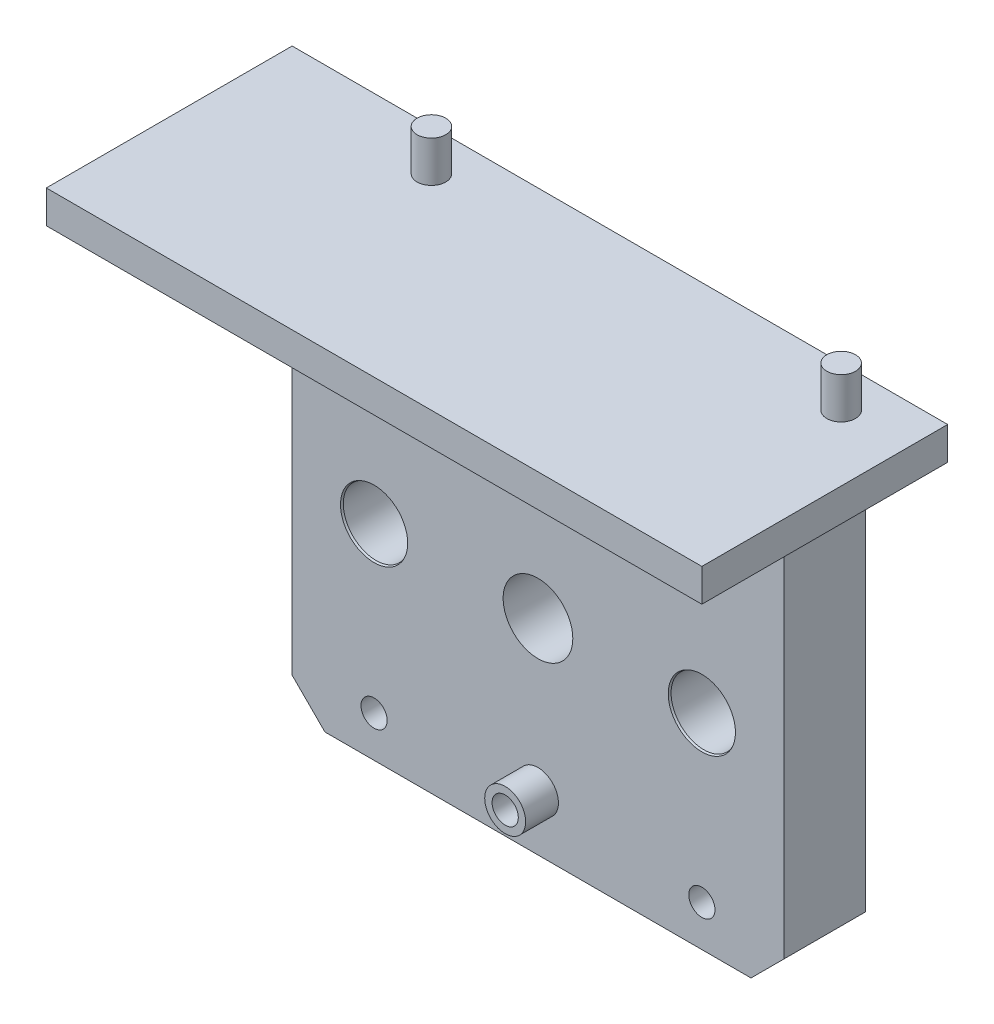
SolidWorks part; units mm, degrees
ref_plane "前视基准面" through (0, 0, 0) normal (0, 0, 1) x (1, 0, 0)
ref_plane "上视基准面" through (0, 0, 0) normal (0, 1, 0) x (1, 0, 0)
ref_plane "右视基准面" through (0, 0, 0) normal (1, 0, 0) x (0, 0, -1)
other "Configuration Table"
sketch "草图1" plane through (0, 0, 0) normal (0, 0, 1) x (1, 0, 0)
  line L1 (-30, -25) -> (30, -25)
  line L2 (-30, -25) -> (-30, 25)
  line L3 (-30, 25) -> (30, 25)
  line L4 (30, -25) -> (30, 25)
  line L5 (-30, -25) -> (30, 25) construction
  line L6 (-30, 25) -> (30, -25) construction
  point P0 (0, 0)
  dimension "D1" = 50
  dimension "D2" = 60
extrude "凸台-拉伸1" add sketch "草图1" along normal blind 10
hole_wizard "孔1" positions "草图2" profile "草图3" legacy
sketch "草图2" plane through (0, 0, 10) normal (0, 0, 1) x (1, 0, 0)
  point P0 (0, 0)
sketch "草图3" plane through (0, 0, 10) normal (1, 0, 0) x (0, -1, 0)
  line L0 (0, 0) -> (0, 20)
  line L1 (0, 20) -> (4.25, 20)
  line L2 (4.25, 20) -> (4.25, 0)
  line L3 (4.25, 0) -> (0, 0)
  line L4 (0, 110) -> (0, -10) construction
  dimension "直径" = 8.5
  dimension "深度" = 20
hole_wizard "孔2" positions "草图4" profile "草图5" legacy end condition through all
sketch "草图4" plane through (0, 0, 10) normal (0, 0, 1) x (1, 0, 0)
  point P0 (20, 0)
  point P2 (-20, 0)
  dimension "D1" = 20
  dimension "D2" = 20
sketch "草图5" plane through (20, 0, 10) normal (1, 0, 0) x (0, -1, 0)
  line L0 (0, 0) -> (0, 10)
  line L1 (0, 10) -> (4, 10)
  line L2 (4, 10) -> (4, 0.2414)
  line L3 (4, 0.2414) -> (4.1, 0)
  line L4 (4.1, 0) -> (0, 0)
  line L5 (0, -6.4453) -> (0, 115.525) construction
  line L6 (-4, 0.2414) -> (-4.1, 0) construction
  dimension "直径" = 8
  dimension "深度" = 10
  dimension "锥坑角度" = 45
  dimension "锥坑直径" = 8.2
sketch "草图9" plane through (0, 0, 10) normal (0, 0, 1) x (1, 0, 0)
  circle A0 centre (0, 18.25) radius 2.5
  circle A1 centre (0, -18.25) radius 2.5
  dimension "D1" = 5
  dimension "D2" = 5
  dimension "D3" = 18.25
  dimension "D4" = 18.25
extrude "凸台-拉伸3" add sketch "草图9" along normal blind 4
hole_wizard "孔3" positions "草图10" profile "草图11" legacy end condition through all
sketch "草图10" plane through (0, 0, 14) normal (0, 0, 1) x (1, 0, 0)
  point P0 (0, 18.25)
  point P3 (0, -18.25)
sketch "草图11" plane through (0, 18.25, 14) normal (1, 0, 0) x (0, -1, 0)
  line L0 (0, 0) -> (0, 14)
  line L1 (0, 14) -> (1.6, 14)
  line L2 (1.6, 14) -> (1.6, 0)
  line L3 (1.6, 0) -> (0, 0)
  line L4 (0, 110) -> (0, -10) construction
  dimension "直径" = 3.2
  dimension "深度" = 14
sketch "草图15" plane through (0, 0, 10) normal (0, 0, 1) x (1, 0, 0)
  line L0 (-30, 0) -> (30, 0)
  line L1 (-30, 25) -> (-30, -25) construction
  line L2 (30, -25) -> (30, 25) construction
  line L3 (0, 25) -> (0, -25)
  line L4 (30, 25) -> (-30, 25) construction
  line L5 (-30, -25) -> (30, -25) construction
  line L6 (0, 0) -> (-29.5019, 29.5019)
  line L8 (30, 14.0027) -> (14.0027, 14.0027)
  line L9 (-30, 25) -> (-14.0027, 25)
  line L10 (-30, 25) -> (-30, 14.0027)
  line L11 (-30, 14.0027) -> (-14.0027, 14.0027)
  line L12 (-14.0027, 25) -> (-14.0027, 14.0027)
  line L13 (14.0027, 25) -> (14.0027, 14.0027)
  line L14 (30, 25) -> (14.0027, 25)
  line L15 (30, 25) -> (30, 14.0027)
  line L16 (-30, -14.0027) -> (-14.0027, -14.0027)
  line L17 (-14.0027, -25) -> (-14.0027, -14.0027)
  line L18 (-30, -25) -> (-14.0027, -25)
  line L19 (-30, -25) -> (-30, -14.0027)
  line L20 (30, -25) -> (30, -14.0027)
  line L21 (30, -25) -> (14.0027, -25)
  line L22 (14.0027, -25) -> (14.0027, -14.0027)
  line L23 (30, -14.0027) -> (14.0027, -14.0027)
  circle A0 centre (-20, 20) radius 1.6
  circle A1 centre (20, 20) radius 1.6
  circle A2 centre (20, -20) radius 1.6
  circle A3 centre (-20, -20) radius 1.6
  dimension "D3" = 3.2
  dimension "D1" = 45
  dimension "D2" = 40
chamfer "倒角1" distance 4 angle 45 2 edges at (30, -25, 5) (-30, -25, 5)
extrude "切除-拉伸1" cut sketch "草图15" against normal through all contours L6 A0 | L6 A0 | A1 | A2 | A3 region at (-20.4802, 19.5198, 10) region at (-19.5198, 20.4802, 10) region at (20, 20, 10) region at (20, -20, 10)
sketch "草图16" plane through (0, 25, 0) normal (0, 1, 0) x (1, 0, 0)
  line L2 (30, -10) -> (-30, -10)
  line L3 (30, -10) -> (30, 0)
  line L4 (30, 0) -> (-30, 0)
  line L5 (-30, -10) -> (-30, 0)
extrude "凸台-拉伸4" add sketch "草图16" along normal blind 10.5
sketch "草图17" plane through (0, 35.5, 0) normal (0, 1, 0) x (1, 0, 0)
  line L1 (40, 0) -> (-40, 0)
  line L3 (40, 0) -> (40, -30)
  line L4 (40, -30) -> (-40, -30)
  line L5 (-40, 0) -> (-40, -30)
  line L6 (8, 0) -> (-40, -30) construction
  line L7 (40, -30) -> (-8, 0) construction
  point P0 (0, -5)
  dimension "D1" = 80
  dimension "D2" = 30
extrude "凸台-拉伸5" add sketch "草图17" against normal blind 4
sketch "草图18" plane through (0, 35.5, 0) normal (0, 1, 0) x (1, 0, 0)
  circle A0 centre (32, -5) radius 1.75
  circle A1 centre (-18, -5) radius 1.75
  dimension "D1" = 3.5
  dimension "D2" = 3.5
extrude "凸台-拉伸6" add sketch "草图18" along normal blind 5
